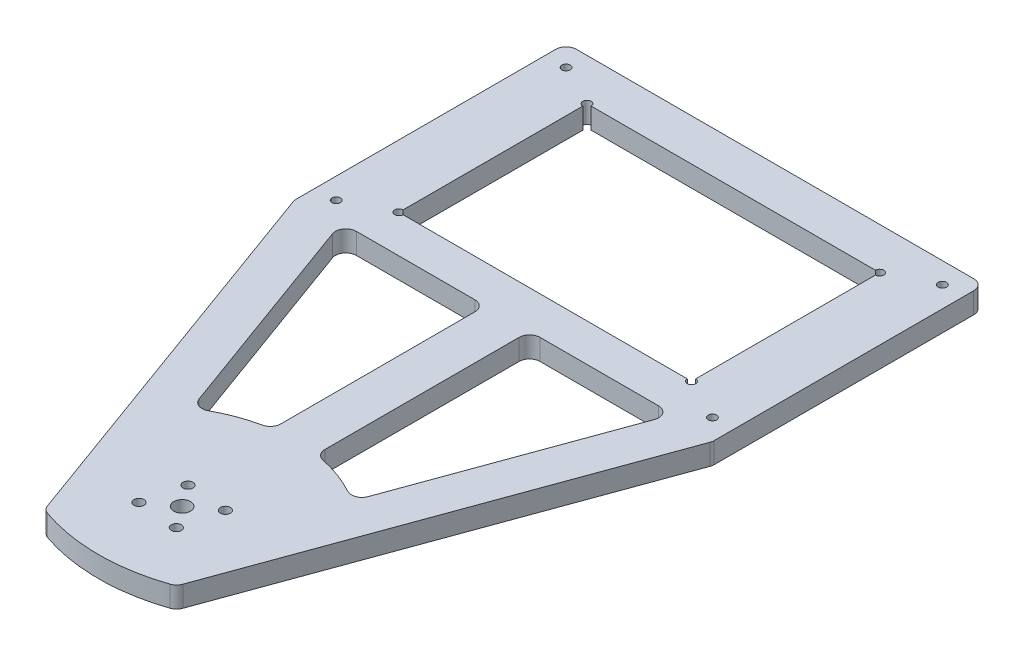
SolidWorks part; units mm, degrees
material "PE High Density"
ref_plane "Front Plane" through (0, 0, 0) normal (0, 0, 1) x (1, 0, 0)
ref_plane "Top Plane" through (0, 0, 0) normal (0, 1, 0) x (1, 0, 0)
ref_plane "Right Plane" through (0, 0, 0) normal (1, 0, 0) x (0, 0, -1)
sketch "Sketch1" plane through (0, 0, 0) normal (0, 1, 0) x (1, 0, 0)
  line L0 (-63.5, -41.275) -> (-20.0634, -160.616)
  line L1 (-63.5, 41.275) -> (63.5, 41.275)
  line L2 (-63.5, 41.275) -> (-63.5, -41.275)
  line L3 (-63.5, -41.275) -> (63.5, -41.275)
  line L4 (63.5, 41.275) -> (63.5, -41.275)
  line L5 (-63.5, 41.275) -> (63.5, -41.275) construction
  line L6 (-63.5, -41.275) -> (63.5, 41.275) construction
  line L7 (63.5, -41.275) -> (20.0634, -160.616)
  arc A0 (-20.0634, -160.616) -> (20.0634, -160.616) centre (0, -107.1035) ccw
  point P0 (0, 0)
  point P9 (-7.2458, -160.5731)
  point P10 (8.5698, -160.5731)
  dimension "D7" = 57.15
  dimension "D1" = 127
  dimension "D2" = 82.55
  dimension "D3" = 70
  dimension "D4" = 70
  dimension "D5" = 127
  dimension "D6" = 127
extrude "Boss-Extrude2" add sketch "Sketch1" along normal blind 6.35 contours L0 A0 L7 L3 | L4 L1 L2 L3 region at (0, 0, 91.3016) region at (0, 0, 0)
sketch "Sketch4" plane through (0, 6.35, 0) normal (0, 1, 0) x (1, 0, 0)
  line L0 (0, -164.2535) -> (0, -138.8535) construction
  line L1 (-7.6031, -144.3775) -> (7.6031, -133.3295)
  line L2 (-4.7029, -132.3806) -> (4.7029, -145.3265)
  arc A1 (-20.0634, -160.616) -> (20.0634, -160.616) centre (0, -107.1035) ccw construction
  circle A7 centre (-4.7029, -132.3806) radius 1.524
  circle A8 centre (7.6031, -133.3295) radius 1.524
  circle A9 centre (4.7029, -145.3265) radius 1.524
  circle A10 centre (-7.6031, -144.3775) radius 1.524
  point P6 (0, -138.8535)
  point P8 (0, -138.8535)
  dimension "D1" = 18.796
  dimension "D2" = 16.002
  dimension "D4" = 3.048
  dimension "D3" = 25.4
  dimension "D5" = 36
extrude "Cut-Extrude5" cut sketch "Sketch4" against normal through all both and the other way through all contours A9 | A10 | A8 | A7 region at (-6.0224, 6.35, 131.7083) region at (7.1455, 6.35, 131.9211) region at (5.3752, 6.35, 144.007) region at (-6.1947, 6.35, 143.9199)
sketch "Sketch5" plane through (0, 6.35, 0) normal (0, 1, 0) x (1, 0, 0)
  line L0 (-63.5, 41.275) -> (-63.5, -41.275) construction
  line L1 (-63.5, 41.275) -> (63.5, 41.275) construction
  circle A0 centre (-57.15, 34.925) radius 1.27
  circle A1 centre (-57.15, -34.925) radius 1.27
  dimension "D1" = 2.54
  dimension "D4" = 2.54
  dimension "D6" = 76.2
  dimension "D2" = 6.35
  dimension "D3" = 6.35
  dimension "D5" = 6.35
extrude "Cut-Extrude7" cut sketch "Sketch5" against normal through all
mirror "Mirror2" about plane through (0, 0, 0) normal (1, 0, 0) of "Cut-Extrude7"
sketch "Sketch7" plane through (0, 6.35, 0) normal (0, 1, 0) x (1, 0, 0)
  line L0 (-63.5, 41.275) -> (63.5, 41.275) construction
  line L1 (-44.45, 28.575) -> (44.45, 28.575)
  line L2 (-44.45, 28.575) -> (-44.45, -28.575)
  line L3 (-44.45, -28.575) -> (44.45, -28.575)
  line L4 (44.45, 28.575) -> (44.45, -28.575)
  line L5 (-44.45, 28.575) -> (44.45, -28.575) construction
  line L6 (-44.45, -28.575) -> (44.45, 28.575) construction
  line L7 (63.5, 41.275) -> (63.5, -41.275) construction
  circle A0 centre (-44.45, 28.575) radius 1.27
  circle A1 centre (-44.45, -28.575) radius 1.27
  circle A2 centre (44.45, -28.575) radius 1.27
  circle A3 centre (44.45, 28.575) radius 1.27
  point P0 (0, 0)
  dimension "D3" = 2.54
  dimension "D1" = 12.7
  dimension "D2" = 19.05
extrude "Cut-Extrude9" cut sketch "Sketch7" against normal through all both and the other way through all contours A3 L1 A0 L2 A1 L3 A2 L4 | L1 A0 L2 | L2 A0 L1 | L2 A1 L3 | L3 A1 L2 | L3 A2 L4 | L4 A2 L3 | L4 A3 L1 | L4 L3 L2 L1 region at (-44.6297, 6.35, -28.7547) region at (-43.911, 6.35, -28.036) region at (0, 6.35, 0) region at (44.6297, 6.35, -28.7547) region at (-43.911, 6.35, 28.036) region at (-44.6297, 6.35, 28.7547) region at (44.6297, 6.35, 28.7547) region at (43.911, 6.35, 28.036)
sketch "Sketch8" plane through (0, 6.35, 0) normal (0, 1, 0) x (1, 0, 0)
  line L0 (-50.4367, -40.0338) -> (-24.3748, -111.6384)
  line L7 (50.4367, -40.0338) -> (24.3748, -111.6384)
  line L8 (63.5, -41.275) -> (20.0634, -160.616) construction
  line L9 (-63.5, -41.275) -> (-20.0634, -160.616) construction
  line L10 (-50.4367, -40.0338) -> (50.4367, -40.0338)
  line L12 (6.7133, -40.0338) -> (6.7133, -104.8341)
  line L13 (-6.7133, -40.0338) -> (-6.7133, -104.8341)
  arc A1 (-24.3748, -111.6384) -> (24.3748, -111.6384) centre (0, -148.583) cw
  point P13 (-6.7133, -104.8341)
  dimension "D3" = 44.261
  dimension "D1" = 76.2
  dimension "D2" = 76.2
  dimension "D4" = 12.7
  dimension "D5" = 12.7
  dimension "D6" = 57.15
  dimension "D7" = 57.15
extrude "Cut-Extrude10" cut sketch "Sketch8" against normal through all both and the other way through all contours L0 A1 L12 L10 | L13 A1 L7 L10 region at (-23.3196, 6.35, 69.4517) region at (23.3196, 6.35, 69.4517)
fillet "Fillet5" radius 3.175 10 edges at (50.4367, 3.175, 40.0338) (24.3748, 3.175, 111.6384) (-6.7133, 3.175, 104.8341) (-6.7133, 3.175, 40.0338) (6.7133, 3.175, 40.0338) (6.7133, 3.175, 104.8341) (-24.3748, 3.175, 111.6384) (-50.4367, 3.175, 40.0338) (-63.5, 3.175, -41.275) (63.5, 3.175, -41.275)
sketch "Sketch10" plane through (0, 6.35, 0) normal (0, 1, 0) x (1, 0, 0)
  line L0 (-4.7029, -132.3806) -> (4.7029, -145.3265) construction
  line L1 (7.6031, -133.3295) -> (-7.6031, -144.3775) construction
  circle A0 centre (0, -138.8535) radius 2.54
  point P8 (0, -138.8535)
  dimension "D1" = 5.08
extrude "Cut-Extrude11" cut sketch "Sketch10" against normal through all both and the other way through all
fillet "Fillet9" radius 3.175 4 edges at (-63.5, 3.175, 41.275) (63.5, 3.175, 41.275) (20.0634, 3.175, 160.616) (-20.0634, 3.175, 160.616)
